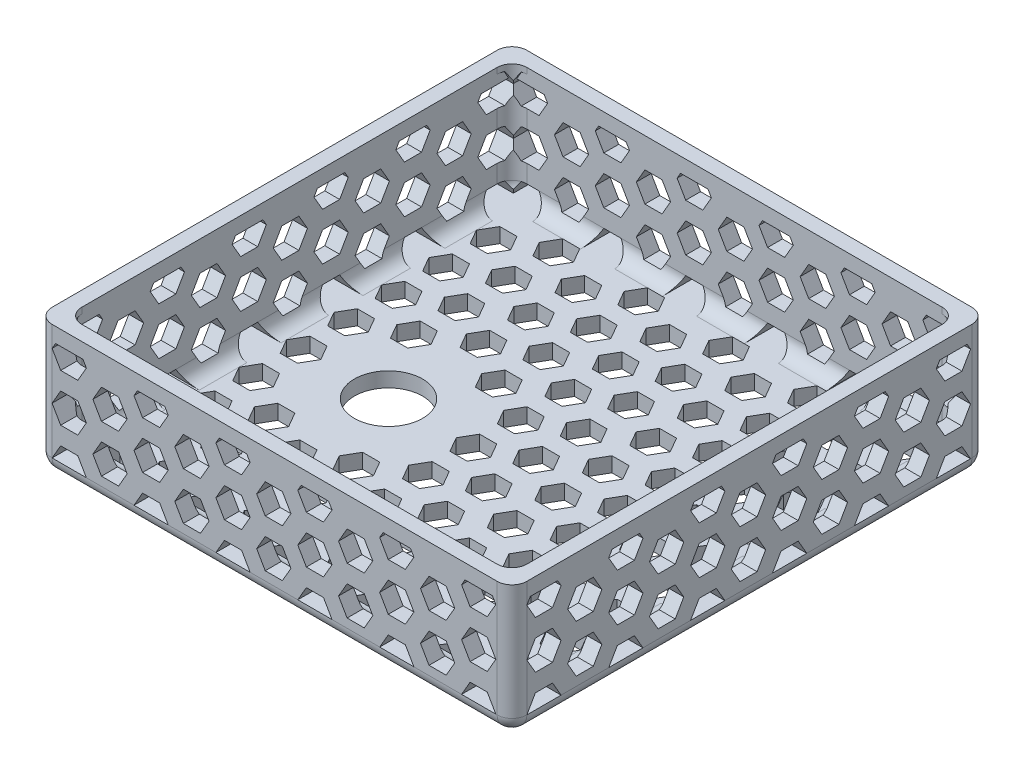
SolidWorks part; units mm, degrees
ref_plane "Front Plane" through (0, 0, 0) normal (0, 0, 1) x (1, 0, 0)
ref_plane "Top Plane" through (0, 0, 0) normal (0, 1, 0) x (1, 0, 0)
ref_plane "Right Plane" through (0, 0, 0) normal (1, 0, 0) x (0, 0, -1)
sketch "Sketch1" plane through (0, 0, 0) normal (0, 1, 0) x (1, 0, 0)
  line L1 (0, 0) -> (80, 0)
  line L2 (0, 0) -> (0, 80)
  line L3 (0, 80) -> (80, 80)
  line L4 (80, 0) -> (80, 80)
  dimension "D1" = 80
  dimension "D2" = 80
extrude "Boss-Extrude1" add sketch "Sketch1" along normal blind 22
sketch "Sketch2" plane through (0, 22, 0) normal (0, 1, 0) x (1, 0, 0)
  line L0 (0, 80) -> (0, 0) construction
  line L1 (2.5, 77.5) -> (77.5, 77.5)
  line L2 (2.5, 77.5) -> (2.5, 2.5)
  line L3 (2.5, 2.5) -> (77.5, 2.5)
  line L4 (77.5, 77.5) -> (77.5, 2.5)
  line L5 (80, 0) -> (80, 80) construction
  line L6 (0, 0) -> (80, 0) construction
  line L7 (80, 80) -> (0, 80) construction
  dimension "D1" = 2.5
  dimension "D2" = 2.5
  dimension "D3" = 2.5
  dimension "D4" = 2.5
extrude "Cut-Extrude1" cut sketch "Sketch2" against normal blind 19.5
fillet "Fillet1" radius 2.5 16 edges at (40, 0, -80) (80, 11, -80) (80, 0, -40) (80, 11, 0) (40, 0, 0) (0, 0, -40) (0, 11, -80) (0, 11, 0) (77.5, 12.25, -77.5) (2.5, 12.25, -2.5) (40, 2.5, -2.5) (77.5, 2.5, -40) (77.5, 12.25, -2.5) (2.5, 2.5, -40) (40, 2.5, -77.5) (2.5, 12.25, -77.5)
ref_plane "Plane1" through (40, 0, 0) normal (1, 0, 0) x (0, 0, -1)
sketch "Sketch6" plane through (40, 0, 0) normal (1, 0, 0) x (0, 0, -1)
  line L0 (40, 22) -> (40, 2.5) construction
  line L1 (5, 22) -> (75, 22) construction
  line L2 (5, 2.5) -> (75, 2.5) construction
ref_plane "Plane2" through (0, 0, 0) normal (-0.7071, 0, -0.7071) x (-0.7071, 0, 0.7071)
ref_plane "Plane3" through (0.7322, 0, -0.7322) normal (-0.7071, 0, 0.7071) x (0.7071, 0, 0.7071)
sketch "Sketch10" plane through (0, 2.5, 0) normal (0, 1, 0) x (1, 0, 0)
  line L0 (5, 5) -> (75, 5) construction
  line L4 (10.7735, 5) -> (9.3301, 7.5)
  line L5 (9.3301, 7.5) -> (6.4434, 7.5)
  line L6 (6.4434, 7.5) -> (5, 5)
  line L7 (5, 75) -> (5, 5) construction
  line L15 (25.0735, 5) -> (23.6301, 7.5)
  line L16 (23.6301, 7.5) -> (20.7434, 7.5)
  line L17 (20.7434, 7.5) -> (19.3, 5)
  line L20 (13.5265, 6) -> (16.4132, 6)
  line L21 (16.4132, 6) -> (17.8566, 8.5)
  line L22 (17.8566, 8.5) -> (16.4132, 11)
  line L23 (16.4132, 11) -> (13.5265, 11)
  line L24 (13.5265, 11) -> (12.0831, 8.5)
  line L25 (12.0831, 8.5) -> (13.5265, 6)
  line L27 (39.3735, 5) -> (37.9301, 7.5)
  line L28 (37.9301, 7.5) -> (35.0434, 7.5)
  line L29 (35.0434, 7.5) -> (33.6, 5)
  line L32 (27.8265, 6) -> (30.7132, 6)
  line L33 (30.7132, 6) -> (32.1566, 8.5)
  line L34 (32.1566, 8.5) -> (30.7132, 11)
  line L35 (30.7132, 11) -> (27.8265, 11)
  line L36 (27.8265, 11) -> (26.3831, 8.5)
  line L37 (26.3831, 8.5) -> (27.8265, 6)
  line L39 (53.6735, 5) -> (52.2301, 7.5)
  line L40 (52.2301, 7.5) -> (49.3434, 7.5)
  line L41 (49.3434, 7.5) -> (47.9, 5)
  line L44 (42.1265, 6) -> (45.0132, 6)
  line L45 (45.0132, 6) -> (46.4566, 8.5)
  line L46 (46.4566, 8.5) -> (45.0132, 11)
  line L47 (45.0132, 11) -> (42.1265, 11)
  line L48 (42.1265, 11) -> (40.6831, 8.5)
  line L49 (40.6831, 8.5) -> (42.1265, 6)
  line L51 (67.9735, 5) -> (66.5301, 7.5)
  line L52 (66.5301, 7.5) -> (63.6434, 7.5)
  line L53 (63.6434, 7.5) -> (62.2, 5)
  line L56 (56.4265, 6) -> (59.3132, 6)
  line L57 (59.3132, 6) -> (60.7566, 8.5)
  line L58 (60.7566, 8.5) -> (59.3132, 11)
  line L59 (59.3132, 11) -> (56.4265, 11)
  line L60 (56.4265, 11) -> (54.9831, 8.5)
  line L61 (54.9831, 8.5) -> (56.4265, 6)
  line L68 (70.7265, 6) -> (73.6132, 6)
  line L69 (73.6132, 6) -> (75.0566, 8.5)
  line L70 (75.0566, 8.5) -> (73.6132, 11)
  line L71 (73.6132, 11) -> (70.7265, 11)
  line L72 (70.7265, 11) -> (69.2831, 8.5)
  line L73 (69.2831, 8.5) -> (70.7265, 6)
  line L74 (23.6301, 10.5) -> (25.0735, 13)
  line L75 (25.0735, 13) -> (23.6301, 15.5)
  line L76 (23.6301, 15.5) -> (20.7434, 15.5)
  line L77 (20.7434, 15.5) -> (19.3, 13)
  line L78 (19.3, 13) -> (20.7434, 10.5)
  line L79 (20.7434, 10.5) -> (23.6301, 10.5)
  line L80 (13.5265, 14) -> (16.4132, 14)
  line L81 (16.4132, 14) -> (17.8566, 16.5)
  line L82 (17.8566, 16.5) -> (16.4132, 19)
  line L83 (16.4132, 19) -> (13.5265, 19)
  line L84 (13.5265, 19) -> (12.0831, 16.5)
  line L85 (12.0831, 16.5) -> (13.5265, 14)
  line L86 (37.9301, 10.5) -> (39.3735, 13)
  line L87 (39.3735, 13) -> (37.9301, 15.5)
  line L88 (37.9301, 15.5) -> (35.0434, 15.5)
  line L89 (35.0434, 15.5) -> (33.6, 13)
  line L90 (33.6, 13) -> (35.0434, 10.5)
  line L91 (35.0434, 10.5) -> (37.9301, 10.5)
  line L92 (27.8265, 14) -> (30.7132, 14)
  line L93 (30.7132, 14) -> (32.1566, 16.5)
  line L94 (32.1566, 16.5) -> (30.7132, 19)
  line L95 (30.7132, 19) -> (27.8265, 19)
  line L96 (27.8265, 19) -> (26.3831, 16.5)
  line L97 (26.3831, 16.5) -> (27.8265, 14)
  line L98 (52.2301, 10.5) -> (53.6735, 13)
  line L99 (53.6735, 13) -> (52.2301, 15.5)
  line L100 (52.2301, 15.5) -> (49.3434, 15.5)
  line L101 (49.3434, 15.5) -> (47.9, 13)
  line L102 (47.9, 13) -> (49.3434, 10.5)
  line L103 (49.3434, 10.5) -> (52.2301, 10.5)
  line L104 (42.1265, 14) -> (45.0132, 14)
  line L105 (45.0132, 14) -> (46.4566, 16.5)
  line L106 (46.4566, 16.5) -> (45.0132, 19)
  line L107 (45.0132, 19) -> (42.1265, 19)
  line L108 (42.1265, 19) -> (40.6831, 16.5)
  line L109 (40.6831, 16.5) -> (42.1265, 14)
  line L110 (66.5301, 10.5) -> (67.9735, 13)
  line L111 (67.9735, 13) -> (66.5301, 15.5)
  line L112 (66.5301, 15.5) -> (63.6434, 15.5)
  line L113 (63.6434, 15.5) -> (62.2, 13)
  line L114 (62.2, 13) -> (63.6434, 10.5)
  line L115 (63.6434, 10.5) -> (66.5301, 10.5)
  line L116 (56.4265, 14) -> (59.3132, 14)
  line L117 (59.3132, 14) -> (60.7566, 16.5)
  line L118 (60.7566, 16.5) -> (59.3132, 19)
  line L119 (59.3132, 19) -> (56.4265, 19)
  line L120 (56.4265, 19) -> (54.9831, 16.5)
  line L121 (54.9831, 16.5) -> (56.4265, 14)
  line L128 (70.7265, 14) -> (73.6132, 14)
  line L129 (73.6132, 14) -> (75.0566, 16.5)
  line L130 (75.0566, 16.5) -> (73.6132, 19)
  line L131 (73.6132, 19) -> (70.7265, 19)
  line L132 (70.7265, 19) -> (69.2831, 16.5)
  line L133 (69.2831, 16.5) -> (70.7265, 14)
  line L134 (23.6301, 18.5) -> (25.0735, 21)
  line L135 (25.0735, 21) -> (23.6301, 23.5)
  line L136 (23.6301, 23.5) -> (20.7434, 23.5)
  line L137 (20.7434, 23.5) -> (19.3, 21)
  line L138 (19.3, 21) -> (20.7434, 18.5)
  line L139 (20.7434, 18.5) -> (23.6301, 18.5)
  line L140 (13.5265, 22) -> (16.4132, 22)
  line L141 (16.4132, 22) -> (17.8566, 24.5)
  line L142 (17.8566, 24.5) -> (16.4132, 27)
  line L143 (16.4132, 27) -> (13.5265, 27)
  line L144 (13.5265, 27) -> (12.0831, 24.5)
  line L145 (12.0831, 24.5) -> (13.5265, 22)
  line L146 (37.9301, 18.5) -> (39.3735, 21)
  line L147 (39.3735, 21) -> (37.9301, 23.5)
  line L148 (37.9301, 23.5) -> (35.0434, 23.5)
  line L149 (35.0434, 23.5) -> (33.6, 21)
  line L150 (33.6, 21) -> (35.0434, 18.5)
  line L151 (35.0434, 18.5) -> (37.9301, 18.5)
  line L152 (27.8265, 22) -> (30.7132, 22)
  line L153 (30.7132, 22) -> (32.1566, 24.5)
  line L154 (32.1566, 24.5) -> (30.7132, 27)
  line L155 (30.7132, 27) -> (27.8265, 27)
  line L156 (27.8265, 27) -> (26.3831, 24.5)
  line L157 (26.3831, 24.5) -> (27.8265, 22)
  line L158 (52.2301, 18.5) -> (53.6735, 21)
  line L159 (53.6735, 21) -> (52.2301, 23.5)
  line L160 (52.2301, 23.5) -> (49.3434, 23.5)
  line L161 (49.3434, 23.5) -> (47.9, 21)
  line L162 (47.9, 21) -> (49.3434, 18.5)
  line L163 (49.3434, 18.5) -> (52.2301, 18.5)
  line L164 (42.1265, 22) -> (45.0132, 22)
  line L165 (45.0132, 22) -> (46.4566, 24.5)
  line L166 (46.4566, 24.5) -> (45.0132, 27)
  line L167 (45.0132, 27) -> (42.1265, 27)
  line L168 (42.1265, 27) -> (40.6831, 24.5)
  line L169 (40.6831, 24.5) -> (42.1265, 22)
  line L170 (66.5301, 18.5) -> (67.9735, 21)
  line L171 (67.9735, 21) -> (66.5301, 23.5)
  line L172 (66.5301, 23.5) -> (63.6434, 23.5)
  line L173 (63.6434, 23.5) -> (62.2, 21)
  line L174 (62.2, 21) -> (63.6434, 18.5)
  line L175 (63.6434, 18.5) -> (66.5301, 18.5)
  line L176 (56.4265, 22) -> (59.3132, 22)
  line L177 (59.3132, 22) -> (60.7566, 24.5)
  line L178 (60.7566, 24.5) -> (59.3132, 27)
  line L179 (59.3132, 27) -> (56.4265, 27)
  line L180 (56.4265, 27) -> (54.9831, 24.5)
  line L181 (54.9831, 24.5) -> (56.4265, 22)
  line L188 (70.7265, 22) -> (73.6132, 22)
  line L189 (73.6132, 22) -> (75.0566, 24.5)
  line L190 (75.0566, 24.5) -> (73.6132, 27)
  line L191 (73.6132, 27) -> (70.7265, 27)
  line L192 (70.7265, 27) -> (69.2831, 24.5)
  line L193 (69.2831, 24.5) -> (70.7265, 22)
  line L206 (37.9301, 26.5) -> (39.3735, 29)
  line L207 (39.3735, 29) -> (37.9301, 31.5)
  line L208 (37.9301, 31.5) -> (35.0434, 31.5)
  line L209 (35.0434, 31.5) -> (33.6, 29)
  line L210 (33.6, 29) -> (35.0434, 26.5)
  line L211 (35.0434, 26.5) -> (37.9301, 26.5)
  line L218 (52.2301, 26.5) -> (53.6735, 29)
  line L219 (53.6735, 29) -> (52.2301, 31.5)
  line L220 (52.2301, 31.5) -> (49.3434, 31.5)
  line L221 (49.3434, 31.5) -> (47.9, 29)
  line L222 (47.9, 29) -> (49.3434, 26.5)
  line L223 (49.3434, 26.5) -> (52.2301, 26.5)
  line L224 (42.1265, 30) -> (45.0132, 30)
  line L225 (45.0132, 30) -> (46.4566, 32.5)
  line L226 (46.4566, 32.5) -> (45.0132, 35)
  line L227 (45.0132, 35) -> (42.1265, 35)
  line L228 (42.1265, 35) -> (40.6831, 32.5)
  line L229 (40.6831, 32.5) -> (42.1265, 30)
  line L230 (66.5301, 26.5) -> (67.9735, 29)
  line L231 (67.9735, 29) -> (66.5301, 31.5)
  line L232 (66.5301, 31.5) -> (63.6434, 31.5)
  line L233 (63.6434, 31.5) -> (62.2, 29)
  line L234 (62.2, 29) -> (63.6434, 26.5)
  line L235 (63.6434, 26.5) -> (66.5301, 26.5)
  line L236 (56.4265, 30) -> (59.3132, 30)
  line L237 (59.3132, 30) -> (60.7566, 32.5)
  line L238 (60.7566, 32.5) -> (59.3132, 35)
  line L239 (59.3132, 35) -> (56.4265, 35)
  line L240 (56.4265, 35) -> (54.9831, 32.5)
  line L241 (54.9831, 32.5) -> (56.4265, 30)
  line L248 (70.7265, 30) -> (73.6132, 30)
  line L249 (73.6132, 30) -> (75.0566, 32.5)
  line L250 (75.0566, 32.5) -> (73.6132, 35)
  line L251 (73.6132, 35) -> (70.7265, 35)
  line L252 (70.7265, 35) -> (69.2831, 32.5)
  line L253 (69.2831, 32.5) -> (70.7265, 30)
  line L266 (37.9301, 34.5) -> (39.3735, 37)
  line L267 (39.3735, 37) -> (37.9301, 39.5)
  line L268 (37.9301, 39.5) -> (35.0434, 39.5)
  line L269 (35.0434, 39.5) -> (33.6, 37)
  line L270 (33.6, 37) -> (35.0434, 34.5)
  line L271 (35.0434, 34.5) -> (37.9301, 34.5)
  line L278 (52.2301, 34.5) -> (53.6735, 37)
  line L279 (53.6735, 37) -> (52.2301, 39.5)
  line L280 (52.2301, 39.5) -> (49.3434, 39.5)
  line L281 (49.3434, 39.5) -> (47.9, 37)
  line L282 (47.9, 37) -> (49.3434, 34.5)
  line L283 (49.3434, 34.5) -> (52.2301, 34.5)
  line L284 (42.1265, 38) -> (45.0132, 38)
  line L285 (45.0132, 38) -> (46.4566, 40.5)
  line L286 (46.4566, 40.5) -> (45.0132, 43)
  line L287 (45.0132, 43) -> (42.1265, 43)
  line L288 (42.1265, 43) -> (40.6831, 40.5)
  line L289 (40.6831, 40.5) -> (42.1265, 38)
  line L290 (66.5301, 34.5) -> (67.9735, 37)
  line L291 (67.9735, 37) -> (66.5301, 39.5)
  line L292 (66.5301, 39.5) -> (63.6434, 39.5)
  line L293 (63.6434, 39.5) -> (62.2, 37)
  line L294 (62.2, 37) -> (63.6434, 34.5)
  line L295 (63.6434, 34.5) -> (66.5301, 34.5)
  line L296 (56.4265, 38) -> (59.3132, 38)
  line L297 (59.3132, 38) -> (60.7566, 40.5)
  line L298 (60.7566, 40.5) -> (59.3132, 43)
  line L299 (59.3132, 43) -> (56.4265, 43)
  line L300 (56.4265, 43) -> (54.9831, 40.5)
  line L301 (54.9831, 40.5) -> (56.4265, 38)
  line L308 (70.7265, 38) -> (73.6132, 38)
  line L309 (73.6132, 38) -> (75.0566, 40.5)
  line L310 (75.0566, 40.5) -> (73.6132, 43)
  line L311 (73.6132, 43) -> (70.7265, 43)
  line L312 (70.7265, 43) -> (69.2831, 40.5)
  line L313 (69.2831, 40.5) -> (70.7265, 38)
  line L320 (13.5265, 46) -> (16.4132, 46)
  line L321 (16.4132, 46) -> (17.8566, 48.5)
  line L322 (17.8566, 48.5) -> (16.4132, 51)
  line L323 (16.4132, 51) -> (13.5265, 51)
  line L324 (13.5265, 51) -> (12.0831, 48.5)
  line L325 (12.0831, 48.5) -> (13.5265, 46)
  line L326 (37.9301, 42.5) -> (39.3735, 45)
  line L327 (39.3735, 45) -> (37.9301, 47.5)
  line L328 (37.9301, 47.5) -> (35.0434, 47.5)
  line L329 (35.0434, 47.5) -> (33.6, 45)
  line L330 (33.6, 45) -> (35.0434, 42.5)
  line L331 (35.0434, 42.5) -> (37.9301, 42.5)
  line L332 (27.8265, 46) -> (30.7132, 46)
  line L333 (30.7132, 46) -> (32.1566, 48.5)
  line L334 (32.1566, 48.5) -> (30.7132, 51)
  line L335 (30.7132, 51) -> (27.8265, 51)
  line L336 (27.8265, 51) -> (26.3831, 48.5)
  line L337 (26.3831, 48.5) -> (27.8265, 46)
  line L338 (52.2301, 42.5) -> (53.6735, 45)
  line L339 (53.6735, 45) -> (52.2301, 47.5)
  line L340 (52.2301, 47.5) -> (49.3434, 47.5)
  line L341 (49.3434, 47.5) -> (47.9, 45)
  line L342 (47.9, 45) -> (49.3434, 42.5)
  line L343 (49.3434, 42.5) -> (52.2301, 42.5)
  line L344 (42.1265, 46) -> (45.0132, 46)
  line L345 (45.0132, 46) -> (46.4566, 48.5)
  line L346 (46.4566, 48.5) -> (45.0132, 51)
  line L347 (45.0132, 51) -> (42.1265, 51)
  line L348 (42.1265, 51) -> (40.6831, 48.5)
  line L349 (40.6831, 48.5) -> (42.1265, 46)
  line L350 (66.5301, 42.5) -> (67.9735, 45)
  line L351 (67.9735, 45) -> (66.5301, 47.5)
  line L352 (66.5301, 47.5) -> (63.6434, 47.5)
  line L353 (63.6434, 47.5) -> (62.2, 45)
  line L354 (62.2, 45) -> (63.6434, 42.5)
  line L355 (63.6434, 42.5) -> (66.5301, 42.5)
  line L356 (56.4265, 46) -> (59.3132, 46)
  line L357 (59.3132, 46) -> (60.7566, 48.5)
  line L358 (60.7566, 48.5) -> (59.3132, 51)
  line L359 (59.3132, 51) -> (56.4265, 51)
  line L360 (56.4265, 51) -> (54.9831, 48.5)
  line L361 (54.9831, 48.5) -> (56.4265, 46)
  line L368 (70.7265, 46) -> (73.6132, 46)
  line L369 (73.6132, 46) -> (75.0566, 48.5)
  line L370 (75.0566, 48.5) -> (73.6132, 51)
  line L371 (73.6132, 51) -> (70.7265, 51)
  line L372 (70.7265, 51) -> (69.2831, 48.5)
  line L373 (69.2831, 48.5) -> (70.7265, 46)
  line L374 (23.6301, 50.5) -> (25.0735, 53)
  line L375 (25.0735, 53) -> (23.6301, 55.5)
  line L376 (23.6301, 55.5) -> (20.7434, 55.5)
  line L377 (20.7434, 55.5) -> (19.3, 53)
  line L378 (19.3, 53) -> (20.7434, 50.5)
  line L379 (20.7434, 50.5) -> (23.6301, 50.5)
  line L380 (13.5265, 54) -> (16.4132, 54)
  line L381 (16.4132, 54) -> (17.8566, 56.5)
  line L382 (17.8566, 56.5) -> (16.4132, 59)
  line L383 (16.4132, 59) -> (13.5265, 59)
  line L384 (13.5265, 59) -> (12.0831, 56.5)
  line L385 (12.0831, 56.5) -> (13.5265, 54)
  line L386 (37.9301, 50.5) -> (39.3735, 53)
  line L387 (39.3735, 53) -> (37.9301, 55.5)
  line L388 (37.9301, 55.5) -> (35.0434, 55.5)
  line L389 (35.0434, 55.5) -> (33.6, 53)
  line L390 (33.6, 53) -> (35.0434, 50.5)
  line L391 (35.0434, 50.5) -> (37.9301, 50.5)
  line L392 (27.8265, 54) -> (30.7132, 54)
  line L393 (30.7132, 54) -> (32.1566, 56.5)
  line L394 (32.1566, 56.5) -> (30.7132, 59)
  line L395 (30.7132, 59) -> (27.8265, 59)
  line L396 (27.8265, 59) -> (26.3831, 56.5)
  line L397 (26.3831, 56.5) -> (27.8265, 54)
  line L398 (52.2301, 50.5) -> (53.6735, 53)
  line L399 (53.6735, 53) -> (52.2301, 55.5)
  line L400 (52.2301, 55.5) -> (49.3434, 55.5)
  line L401 (49.3434, 55.5) -> (47.9, 53)
  line L402 (47.9, 53) -> (49.3434, 50.5)
  line L403 (49.3434, 50.5) -> (52.2301, 50.5)
  line L404 (42.1265, 54) -> (45.0132, 54)
  line L405 (45.0132, 54) -> (46.4566, 56.5)
  line L406 (46.4566, 56.5) -> (45.0132, 59)
  line L407 (45.0132, 59) -> (42.1265, 59)
  line L408 (42.1265, 59) -> (40.6831, 56.5)
  line L409 (40.6831, 56.5) -> (42.1265, 54)
  line L410 (66.5301, 50.5) -> (67.9735, 53)
  line L411 (67.9735, 53) -> (66.5301, 55.5)
  line L412 (66.5301, 55.5) -> (63.6434, 55.5)
  line L413 (63.6434, 55.5) -> (62.2, 53)
  line L414 (62.2, 53) -> (63.6434, 50.5)
  line L415 (63.6434, 50.5) -> (66.5301, 50.5)
  line L416 (56.4265, 54) -> (59.3132, 54)
  line L417 (59.3132, 54) -> (60.7566, 56.5)
  line L418 (60.7566, 56.5) -> (59.3132, 59)
  line L419 (59.3132, 59) -> (56.4265, 59)
  line L420 (56.4265, 59) -> (54.9831, 56.5)
  line L421 (54.9831, 56.5) -> (56.4265, 54)
  line L428 (70.7265, 54) -> (73.6132, 54)
  line L429 (73.6132, 54) -> (75.0566, 56.5)
  line L430 (75.0566, 56.5) -> (73.6132, 59)
  line L431 (73.6132, 59) -> (70.7265, 59)
  line L432 (70.7265, 59) -> (69.2831, 56.5)
  line L433 (69.2831, 56.5) -> (70.7265, 54)
  line L434 (23.6301, 58.5) -> (25.0735, 61)
  line L435 (25.0735, 61) -> (23.6301, 63.5)
  line L436 (23.6301, 63.5) -> (20.7434, 63.5)
  line L437 (20.7434, 63.5) -> (19.3, 61)
  line L438 (19.3, 61) -> (20.7434, 58.5)
  line L439 (20.7434, 58.5) -> (23.6301, 58.5)
  line L440 (13.5265, 62) -> (16.4132, 62)
  line L441 (16.4132, 62) -> (17.8566, 64.5)
  line L442 (17.8566, 64.5) -> (16.4132, 67)
  line L443 (16.4132, 67) -> (13.5265, 67)
  line L444 (13.5265, 67) -> (12.0831, 64.5)
  line L445 (12.0831, 64.5) -> (13.5265, 62)
  line L446 (37.9301, 58.5) -> (39.3735, 61)
  line L447 (39.3735, 61) -> (37.9301, 63.5)
  line L448 (37.9301, 63.5) -> (35.0434, 63.5)
  line L449 (35.0434, 63.5) -> (33.6, 61)
  line L450 (33.6, 61) -> (35.0434, 58.5)
  line L451 (35.0434, 58.5) -> (37.9301, 58.5)
  line L452 (27.8265, 62) -> (30.7132, 62)
  line L453 (30.7132, 62) -> (32.1566, 64.5)
  line L454 (32.1566, 64.5) -> (30.7132, 67)
  line L455 (30.7132, 67) -> (27.8265, 67)
  line L456 (27.8265, 67) -> (26.3831, 64.5)
  line L457 (26.3831, 64.5) -> (27.8265, 62)
  line L458 (52.2301, 58.5) -> (53.6735, 61)
  line L459 (53.6735, 61) -> (52.2301, 63.5)
  line L460 (52.2301, 63.5) -> (49.3434, 63.5)
  line L461 (49.3434, 63.5) -> (47.9, 61)
  line L462 (47.9, 61) -> (49.3434, 58.5)
  line L463 (49.3434, 58.5) -> (52.2301, 58.5)
  line L464 (42.1265, 62) -> (45.0132, 62)
  line L465 (45.0132, 62) -> (46.4566, 64.5)
  line L466 (46.4566, 64.5) -> (45.0132, 67)
  line L467 (45.0132, 67) -> (42.1265, 67)
  line L468 (42.1265, 67) -> (40.6831, 64.5)
  line L469 (40.6831, 64.5) -> (42.1265, 62)
  line L470 (66.5301, 58.5) -> (67.9735, 61)
  line L471 (67.9735, 61) -> (66.5301, 63.5)
  line L472 (66.5301, 63.5) -> (63.6434, 63.5)
  line L473 (63.6434, 63.5) -> (62.2, 61)
  line L474 (62.2, 61) -> (63.6434, 58.5)
  line L475 (63.6434, 58.5) -> (66.5301, 58.5)
  line L476 (56.4265, 62) -> (59.3132, 62)
  line L477 (59.3132, 62) -> (60.7566, 64.5)
  line L478 (60.7566, 64.5) -> (59.3132, 67)
  line L479 (59.3132, 67) -> (56.4265, 67)
  line L480 (56.4265, 67) -> (54.9831, 64.5)
  line L481 (54.9831, 64.5) -> (56.4265, 62)
  line L488 (70.7265, 62) -> (73.6132, 62)
  line L489 (73.6132, 62) -> (75.0566, 64.5)
  line L490 (75.0566, 64.5) -> (73.6132, 67)
  line L491 (73.6132, 67) -> (70.7265, 67)
  line L492 (70.7265, 67) -> (69.2831, 64.5)
  line L493 (69.2831, 64.5) -> (70.7265, 62)
  line L494 (23.6301, 66.5) -> (25.0735, 69)
  line L495 (25.0735, 69) -> (23.6301, 71.5)
  line L496 (23.6301, 71.5) -> (20.7434, 71.5)
  line L497 (20.7434, 71.5) -> (19.3, 69)
  line L498 (19.3, 69) -> (20.7434, 66.5)
  line L499 (20.7434, 66.5) -> (23.6301, 66.5)
  line L500 (13.5265, 70) -> (16.4132, 70)
  line L501 (16.4132, 70) -> (17.8566, 72.5)
  line L502 (17.8566, 72.5) -> (16.4132, 75)
  line L503 (16.4132, 75) -> (13.5265, 75)
  line L504 (13.5265, 75) -> (12.0831, 72.5)
  line L505 (12.0831, 72.5) -> (13.5265, 70)
  line L506 (37.9301, 66.5) -> (39.3735, 69)
  line L507 (39.3735, 69) -> (37.9301, 71.5)
  line L508 (37.9301, 71.5) -> (35.0434, 71.5)
  line L509 (35.0434, 71.5) -> (33.6, 69)
  line L510 (33.6, 69) -> (35.0434, 66.5)
  line L511 (35.0434, 66.5) -> (37.9301, 66.5)
  line L512 (27.8265, 70) -> (30.7132, 70)
  line L513 (30.7132, 70) -> (32.1566, 72.5)
  line L514 (32.1566, 72.5) -> (30.7132, 75)
  line L515 (30.7132, 75) -> (27.8265, 75)
  line L516 (27.8265, 75) -> (26.3831, 72.5)
  line L517 (26.3831, 72.5) -> (27.8265, 70)
  line L518 (52.2301, 66.5) -> (53.6735, 69)
  line L519 (53.6735, 69) -> (52.2301, 71.5)
  line L520 (52.2301, 71.5) -> (49.3434, 71.5)
  line L521 (49.3434, 71.5) -> (47.9, 69)
  line L522 (47.9, 69) -> (49.3434, 66.5)
  line L523 (49.3434, 66.5) -> (52.2301, 66.5)
  line L524 (42.1265, 70) -> (45.0132, 70)
  line L525 (45.0132, 70) -> (46.4566, 72.5)
  line L526 (46.4566, 72.5) -> (45.0132, 75)
  line L527 (45.0132, 75) -> (42.1265, 75)
  line L528 (42.1265, 75) -> (40.6831, 72.5)
  line L529 (40.6831, 72.5) -> (42.1265, 70)
  line L530 (66.5301, 66.5) -> (67.9735, 69)
  line L531 (67.9735, 69) -> (66.5301, 71.5)
  line L532 (66.5301, 71.5) -> (63.6434, 71.5)
  line L533 (63.6434, 71.5) -> (62.2, 69)
  line L534 (62.2, 69) -> (63.6434, 66.5)
  line L535 (63.6434, 66.5) -> (66.5301, 66.5)
  line L536 (56.4265, 70) -> (59.3132, 70)
  line L537 (59.3132, 70) -> (60.7566, 72.5)
  line L538 (60.7566, 72.5) -> (59.3132, 75)
  line L539 (59.3132, 75) -> (56.4265, 75)
  line L540 (56.4265, 75) -> (54.9831, 72.5)
  line L541 (54.9831, 72.5) -> (56.4265, 70)
  line L548 (70.7265, 70) -> (73.6132, 70)
  line L549 (73.6132, 70) -> (75.0566, 72.5)
  line L550 (75.0566, 72.5) -> (73.6132, 75)
  line L551 (73.6132, 75) -> (70.7265, 75)
  line L552 (70.7265, 75) -> (69.2831, 72.5)
  line L553 (69.2831, 72.5) -> (70.7265, 70)
  line L554 (9.3301, 10.5) -> (10.7735, 13)
  line L555 (10.7735, 13) -> (9.3301, 15.5)
  line L556 (9.3301, 15.5) -> (6.4434, 15.5)
  line L557 (6.4434, 15.5) -> (5, 13)
  line L558 (5, 13) -> (6.4434, 10.5)
  line L559 (6.4434, 10.5) -> (9.3301, 10.5)
  line L566 (9.3301, 18.5) -> (10.7735, 21)
  line L567 (10.7735, 21) -> (9.3301, 23.5)
  line L568 (9.3301, 23.5) -> (6.4434, 23.5)
  line L569 (6.4434, 23.5) -> (5, 21)
  line L570 (5, 21) -> (6.4434, 18.5)
  line L571 (6.4434, 18.5) -> (9.3301, 18.5)
  line L578 (9.3301, 26.5) -> (10.7735, 29)
  line L579 (10.7735, 29) -> (9.3301, 31.5)
  line L580 (9.3301, 31.5) -> (6.4434, 31.5)
  line L581 (6.4434, 31.5) -> (5, 29)
  line L582 (5, 29) -> (6.4434, 26.5)
  line L583 (6.4434, 26.5) -> (9.3301, 26.5)
  line L590 (9.3301, 34.5) -> (10.7735, 37)
  line L591 (10.7735, 37) -> (9.3301, 39.5)
  line L592 (9.3301, 39.5) -> (6.4434, 39.5)
  line L593 (6.4434, 39.5) -> (5, 37)
  line L594 (5, 37) -> (6.4434, 34.5)
  line L595 (6.4434, 34.5) -> (9.3301, 34.5)
  line L602 (9.3301, 42.5) -> (10.7735, 45)
  line L603 (10.7735, 45) -> (9.3301, 47.5)
  line L604 (9.3301, 47.5) -> (6.4434, 47.5)
  line L605 (6.4434, 47.5) -> (5, 45)
  line L606 (5, 45) -> (6.4434, 42.5)
  line L607 (6.4434, 42.5) -> (9.3301, 42.5)
  line L614 (9.3301, 50.5) -> (10.7735, 53)
  line L615 (10.7735, 53) -> (9.3301, 55.5)
  line L616 (9.3301, 55.5) -> (6.4434, 55.5)
  line L617 (6.4434, 55.5) -> (5, 53)
  line L618 (5, 53) -> (6.4434, 50.5)
  line L619 (6.4434, 50.5) -> (9.3301, 50.5)
  line L626 (9.3301, 58.5) -> (10.7735, 61)
  line L627 (10.7735, 61) -> (9.3301, 63.5)
  line L628 (9.3301, 63.5) -> (6.4434, 63.5)
  line L629 (6.4434, 63.5) -> (5, 61)
  line L630 (5, 61) -> (6.4434, 58.5)
  line L631 (6.4434, 58.5) -> (9.3301, 58.5)
  line L638 (9.3301, 66.5) -> (10.7735, 69)
  line L639 (10.7735, 69) -> (9.3301, 71.5)
  line L640 (9.3301, 71.5) -> (6.4434, 71.5)
  line L641 (6.4434, 71.5) -> (5, 69)
  line L642 (5, 69) -> (6.4434, 66.5)
  line L643 (6.4434, 66.5) -> (9.3301, 66.5)
  line L690 (5, 5) -> (10.7735, 5)
  line L691 (19.3, 5) -> (25.0735, 5)
  line L692 (33.6, 5) -> (39.3735, 5)
  line L693 (47.9, 5) -> (53.6735, 5)
  line L694 (80.8301, 71.5) -> (77.9434, 71.5) [skipped]
  line L696 (82.2735, 69) -> (80.8301, 71.5) [skipped]
  line L697 (77.9434, 71.5) -> (76.5, 69) [skipped]
  line L700 (80.8301, 63.5) -> (77.9434, 63.5) [skipped]
  line L701 (82.2735, 61) -> (80.8301, 63.5) [skipped]
  line L702 (77.9434, 63.5) -> (76.5, 61) [skipped]
  line L704 (80.8301, 55.5) -> (77.9434, 55.5) [skipped]
  line L708 (77.9434, 47.5) -> (76.5, 45) [skipped]
  line L710 (77.9434, 39.5) -> (76.5, 37) [skipped]
  line L712 (77.9434, 31.5) -> (76.5, 29) [skipped]
  line L714 (77.9434, 23.5) -> (76.5, 21) [skipped]
  line L716 (77.9434, 15.5) -> (76.5, 13) [skipped]
  line L718 (77.9434, 7.5) -> (76.5, 5) [skipped]
  line L720 (80.8301, 7.5) -> (77.9434, 7.5) [skipped]
  line L722 (80.8301, 15.5) -> (77.9434, 15.5) [skipped]
  line L724 (80.8301, 23.5) -> (77.9434, 23.5) [skipped]
  line L726 (80.8301, 31.5) -> (77.9434, 31.5) [skipped]
  line L728 (80.8301, 39.5) -> (77.9434, 39.5) [skipped]
  line L730 (80.8301, 47.5) -> (77.9434, 47.5) [skipped]
  line L733 (82.2735, 45) -> (80.8301, 47.5) [skipped]
  line L735 (82.2735, 37) -> (80.8301, 39.5) [skipped]
  line L737 (82.2735, 29) -> (80.8301, 31.5) [skipped]
  line L739 (82.2735, 21) -> (80.8301, 23.5) [skipped]
  line L741 (82.2735, 13) -> (80.8301, 15.5) [skipped]
  line L743 (82.2735, 5) -> (80.8301, 7.5) [skipped]
  line L746 (82.2735, 53) -> (80.8301, 55.5) [skipped]
  line L747 (77.9434, 55.5) -> (76.5, 53) [skipped]
  line L756 (9.3301, 2.5) -> (10.0518, 3.75) [skipped]
  line L757 (5, 5) -> (5.7217, 3.75) [skipped]
  line L758 (7.8868, 2.5) -> (9.3301, 2.5) [skipped]
  line L759 (62.2, 5) -> (67.9735, 5)
  line L760 (20.7434, 31.5) -> (19.3, 29) [skipped]
  line L761 (25.0735, 29) -> (23.6301, 31.5) [skipped]
  line L762 (20.7434, 39.5) -> (19.3, 37) [skipped]
  line L763 (23.6301, 39.5) -> (20.7434, 39.5) [skipped]
  line L764 (25.0735, 37) -> (23.6301, 39.5) [skipped]
  line L765 (23.6301, 31.5) -> (20.7434, 31.5) [skipped]
  line L766 (23.6301, 47.5) -> (20.7434, 47.5) [skipped]
  line L767 (25.0735, 45) -> (23.6301, 47.5) [skipped]
  line L768 (20.7434, 47.5) -> (19.3, 45) [skipped]
  arc A0 (10.0518, 6.25) -> (5.7217, 6.25) centre (7.8868, 5) ccw construction
  circle A1 centre (22.1868, 37) radius 5.75
  dimension "D1" = 11.5
  dimension "D4" = 6
  dimension "D5" = 9
extrude "Cut-Extrude5" cut sketch "Sketch10" against normal blind 2.5
sketch "Sketch11" plane through (0, 0, 0) normal (-1, 0, 0) x (0, 0, 1)
  line L0 (-77.5, 2.5) -> (-2.5, 2.5) construction
  line L4 (-71.7265, 2.5) -> (-73.1699, 5)
  line L5 (-73.1699, 5) -> (-76.0566, 5)
  line L6 (-76.0566, 5) -> (-77.5, 2.5)
  line L7 (-77.5, 22) -> (-77.5, 2.5) construction
  line L8 (-59.3699, 5) -> (-62.2566, 5)
  line L15 (-57.9265, 2.5) -> (-59.3699, 5)
  line L19 (-62.2566, 5) -> (-63.7, 2.5)
  line L20 (-66.2981, 4) -> (-64.8547, 6.5)
  line L21 (-64.8547, 6.5) -> (-66.2981, 9)
  line L22 (-66.2981, 9) -> (-69.1848, 9)
  line L23 (-69.1848, 9) -> (-70.6282, 6.5)
  line L24 (-70.6282, 6.5) -> (-69.1848, 4)
  line L25 (-69.1848, 4) -> (-66.2981, 4)
  line L26 (-45.5699, 5) -> (-48.4566, 5)
  line L27 (-44.1265, 2.5) -> (-45.5699, 5)
  line L31 (-48.4566, 5) -> (-49.9, 2.5)
  line L32 (-52.4981, 4) -> (-51.0547, 6.5)
  line L33 (-51.0547, 6.5) -> (-52.4981, 9)
  line L34 (-52.4981, 9) -> (-55.3848, 9)
  line L35 (-55.3848, 9) -> (-56.8282, 6.5)
  line L36 (-56.8282, 6.5) -> (-55.3848, 4)
  line L37 (-55.3848, 4) -> (-52.4981, 4)
  line L38 (-31.7699, 5) -> (-34.6566, 5)
  line L39 (-30.3265, 2.5) -> (-31.7699, 5)
  line L43 (-34.6566, 5) -> (-36.1, 2.5)
  line L44 (-38.6981, 4) -> (-37.2547, 6.5)
  line L45 (-37.2547, 6.5) -> (-38.6981, 9)
  line L46 (-38.6981, 9) -> (-41.5848, 9)
  line L47 (-41.5848, 9) -> (-43.0282, 6.5)
  line L48 (-43.0282, 6.5) -> (-41.5848, 4)
  line L49 (-41.5848, 4) -> (-38.6981, 4)
  line L50 (-17.9699, 5) -> (-20.8566, 5)
  line L51 (-16.5265, 2.5) -> (-17.9699, 5)
  line L55 (-20.8566, 5) -> (-22.3, 2.5)
  line L56 (-24.8981, 4) -> (-23.4547, 6.5)
  line L57 (-23.4547, 6.5) -> (-24.8981, 9)
  line L58 (-24.8981, 9) -> (-27.7848, 9)
  line L59 (-27.7848, 9) -> (-29.2282, 6.5)
  line L60 (-29.2282, 6.5) -> (-27.7848, 4)
  line L61 (-27.7848, 4) -> (-24.8981, 4)
  line L62 (-4.1699, 5) -> (-7.0566, 5)
  line L63 (-2.7265, 2.5) -> (-4.1699, 5)
  line L67 (-7.0566, 5) -> (-8.5, 2.5)
  line L68 (-11.0981, 4) -> (-9.6547, 6.5)
  line L69 (-9.6547, 6.5) -> (-11.0981, 9)
  line L70 (-11.0981, 9) -> (-13.9848, 9)
  line L71 (-13.9848, 9) -> (-15.4282, 6.5)
  line L72 (-15.4282, 6.5) -> (-13.9848, 4)
  line L73 (-13.9848, 4) -> (-11.0981, 4)
  line L74 (-59.3699, 13) -> (-62.2566, 13)
  line L75 (-57.9265, 10.5) -> (-59.3699, 13)
  line L76 (-59.3699, 8) -> (-57.9265, 10.5)
  line L77 (-62.2566, 8) -> (-59.3699, 8)
  line L78 (-63.7, 10.5) -> (-62.2566, 8)
  line L79 (-62.2566, 13) -> (-63.7, 10.5)
  line L80 (-66.2981, 12) -> (-64.8547, 14.5)
  line L81 (-64.8547, 14.5) -> (-66.2981, 17)
  line L82 (-66.2981, 17) -> (-69.1848, 17)
  line L83 (-69.1848, 17) -> (-70.6282, 14.5)
  line L84 (-70.6282, 14.5) -> (-69.1848, 12)
  line L85 (-69.1848, 12) -> (-66.2981, 12)
  line L86 (-45.5699, 13) -> (-48.4566, 13)
  line L87 (-44.1265, 10.5) -> (-45.5699, 13)
  line L88 (-45.5699, 8) -> (-44.1265, 10.5)
  line L89 (-48.4566, 8) -> (-45.5699, 8)
  line L90 (-49.9, 10.5) -> (-48.4566, 8)
  line L91 (-48.4566, 13) -> (-49.9, 10.5)
  line L92 (-52.4981, 12) -> (-51.0547, 14.5)
  line L93 (-51.0547, 14.5) -> (-52.4981, 17)
  line L94 (-52.4981, 17) -> (-55.3848, 17)
  line L95 (-55.3848, 17) -> (-56.8282, 14.5)
  line L96 (-56.8282, 14.5) -> (-55.3848, 12)
  line L97 (-55.3848, 12) -> (-52.4981, 12)
  line L98 (-31.7699, 13) -> (-34.6566, 13)
  line L99 (-30.3265, 10.5) -> (-31.7699, 13)
  line L100 (-31.7699, 8) -> (-30.3265, 10.5)
  line L101 (-34.6566, 8) -> (-31.7699, 8)
  line L102 (-36.1, 10.5) -> (-34.6566, 8)
  line L103 (-34.6566, 13) -> (-36.1, 10.5)
  line L104 (-38.6981, 12) -> (-37.2547, 14.5)
  line L105 (-37.2547, 14.5) -> (-38.6981, 17)
  line L106 (-38.6981, 17) -> (-41.5848, 17)
  line L107 (-41.5848, 17) -> (-43.0282, 14.5)
  line L108 (-43.0282, 14.5) -> (-41.5848, 12)
  line L109 (-41.5848, 12) -> (-38.6981, 12)
  line L110 (-17.9699, 13) -> (-20.8566, 13)
  line L111 (-16.5265, 10.5) -> (-17.9699, 13)
  line L112 (-17.9699, 8) -> (-16.5265, 10.5)
  line L113 (-20.8566, 8) -> (-17.9699, 8)
  line L114 (-22.3, 10.5) -> (-20.8566, 8)
  line L115 (-20.8566, 13) -> (-22.3, 10.5)
  line L116 (-24.8981, 12) -> (-23.4547, 14.5)
  line L117 (-23.4547, 14.5) -> (-24.8981, 17)
  line L118 (-24.8981, 17) -> (-27.7848, 17)
  line L119 (-27.7848, 17) -> (-29.2282, 14.5)
  line L120 (-29.2282, 14.5) -> (-27.7848, 12)
  line L121 (-27.7848, 12) -> (-24.8981, 12)
  line L122 (-4.1699, 13) -> (-7.0566, 13)
  line L123 (-2.7265, 10.5) -> (-4.1699, 13)
  line L124 (-4.1699, 8) -> (-2.7265, 10.5)
  line L125 (-7.0566, 8) -> (-4.1699, 8)
  line L126 (-8.5, 10.5) -> (-7.0566, 8)
  line L127 (-7.0566, 13) -> (-8.5, 10.5)
  line L128 (-11.0981, 12) -> (-9.6547, 14.5)
  line L129 (-9.6547, 14.5) -> (-11.0981, 17)
  line L130 (-11.0981, 17) -> (-13.9848, 17)
  line L131 (-13.9848, 17) -> (-15.4282, 14.5)
  line L132 (-15.4282, 14.5) -> (-13.9848, 12)
  line L133 (-13.9848, 12) -> (-11.0981, 12)
  line L134 (-59.3699, 21) -> (-62.2566, 21)
  line L135 (-57.9265, 18.5) -> (-59.3699, 21)
  line L136 (-59.3699, 16) -> (-57.9265, 18.5)
  line L137 (-62.2566, 16) -> (-59.3699, 16)
  line L138 (-63.7, 18.5) -> (-62.2566, 16)
  line L139 (-62.2566, 21) -> (-63.7, 18.5)
  line L140 (-66.2981, 20) -> (-64.8547, 22.5)
  line L144 (-70.6282, 22.5) -> (-69.1848, 20)
  line L145 (-69.1848, 20) -> (-66.2981, 20)
  line L146 (-45.5699, 21) -> (-48.4566, 21)
  line L147 (-44.1265, 18.5) -> (-45.5699, 21)
  line L148 (-45.5699, 16) -> (-44.1265, 18.5)
  line L149 (-48.4566, 16) -> (-45.5699, 16)
  line L150 (-49.9, 18.5) -> (-48.4566, 16)
  line L151 (-48.4566, 21) -> (-49.9, 18.5)
  line L152 (-52.4981, 20) -> (-51.0547, 22.5)
  line L156 (-56.8282, 22.5) -> (-55.3848, 20)
  line L157 (-55.3848, 20) -> (-52.4981, 20)
  line L158 (-31.7699, 21) -> (-34.6566, 21)
  line L159 (-30.3265, 18.5) -> (-31.7699, 21)
  line L160 (-31.7699, 16) -> (-30.3265, 18.5)
  line L161 (-34.6566, 16) -> (-31.7699, 16)
  line L162 (-36.1, 18.5) -> (-34.6566, 16)
  line L163 (-34.6566, 21) -> (-36.1, 18.5)
  line L164 (-38.6981, 20) -> (-37.2547, 22.5)
  line L168 (-43.0282, 22.5) -> (-41.5848, 20)
  line L169 (-41.5848, 20) -> (-38.6981, 20)
  line L170 (-17.9699, 21) -> (-20.8566, 21)
  line L171 (-16.5265, 18.5) -> (-17.9699, 21)
  line L172 (-17.9699, 16) -> (-16.5265, 18.5)
  line L173 (-20.8566, 16) -> (-17.9699, 16)
  line L174 (-22.3, 18.5) -> (-20.8566, 16)
  line L175 (-20.8566, 21) -> (-22.3, 18.5)
  line L176 (-24.8981, 20) -> (-23.4547, 22.5)
  line L180 (-29.2282, 22.5) -> (-27.7848, 20)
  line L181 (-27.7848, 20) -> (-24.8981, 20)
  line L182 (-4.1699, 21) -> (-7.0566, 21)
  line L183 (-2.7265, 18.5) -> (-4.1699, 21)
  line L184 (-4.1699, 16) -> (-2.7265, 18.5)
  line L185 (-7.0566, 16) -> (-4.1699, 16)
  line L186 (-8.5, 18.5) -> (-7.0566, 16)
  line L187 (-7.0566, 21) -> (-8.5, 18.5)
  line L188 (-11.0981, 20) -> (-9.6547, 22.5)
  line L192 (-15.4282, 22.5) -> (-13.9848, 20)
  line L193 (-13.9848, 20) -> (-11.0981, 20)
  line L194 (-73.1699, 13) -> (-76.0566, 13)
  line L195 (-71.7265, 10.5) -> (-73.1699, 13)
  line L196 (-73.1699, 8) -> (-71.7265, 10.5)
  line L197 (-76.0566, 8) -> (-73.1699, 8)
  line L198 (-77.5, 10.5) -> (-76.0566, 8)
  line L199 (-76.0566, 13) -> (-77.5, 10.5)
  line L206 (-73.1699, 21) -> (-76.0566, 21)
  line L207 (-71.7265, 18.5) -> (-73.1699, 21)
  line L208 (-73.1699, 16) -> (-71.7265, 18.5)
  line L209 (-76.0566, 16) -> (-73.1699, 16)
  line L210 (-77.5, 18.5) -> (-76.0566, 16)
  line L211 (-76.0566, 21) -> (-77.5, 18.5)
  line L223 (-70.6282, 22.5) -> (-64.8547, 22.5)
  line L229 (-56.8282, 22.5) -> (-51.0547, 22.5)
  line L230 (-43.0282, 22.5) -> (-37.2547, 22.5)
  line L231 (-29.2282, 22.5) -> (-23.4547, 22.5)
  line L242 (-76.7783, 1.25) -> (-76.0566, 0) [skipped]
  line L243 (-73.1699, 0) -> (-72.4482, 1.25) [skipped]
  line L244 (-76.0566, 0) -> (-73.1699, 0) [skipped]
  line L245 (-15.4282, 22.5) -> (-9.6547, 22.5)
  line L246 (-2.7265, 2.5) -> (-8.5, 2.5)
  line L247 (-16.5265, 2.5) -> (-22.3, 2.5)
  line L248 (-30.3265, 2.5) -> (-36.1, 2.5)
  line L249 (-44.1265, 2.5) -> (-49.9, 2.5)
  line L250 (-57.9265, 2.5) -> (-63.7, 2.5)
  line L251 (-71.7265, 2.5) -> (-77.5, 2.5)
  arc A0 (-72.4482, 3.75) -> (-76.7783, 3.75) centre (-74.6132, 2.5) ccw construction
  dimension "D4" = 6
  dimension "D5" = 3
extrude "Cut-Extrude6" cut sketch "Sketch11" against normal blind 5
sketch "Sketch12" plane through (0, 0, 0) normal (-1, 0, 0) x (0, 0, 1)
  line L0 (-2.5, 2.5) -> (-2.5, 22) construction
  line L1 (-77.5, 22) -> (-2.5, 22)
  line L2 (-77.5, 22) -> (-77.5, 19.5)
  line L3 (-77.5, 19.5) -> (-2.5, 19.5)
  line L4 (-2.5, 22) -> (-2.5, 19.5)
  dimension "D1" = 2.5
extrude "Boss-Extrude2" add sketch "Sketch12" against normal blind 2.5
pattern_circular "CirPattern9" count 4 over 360 about axis through (40, 22, -40) along (0, -1, 0) of "Cut-Extrude6", "Boss-Extrude2"
